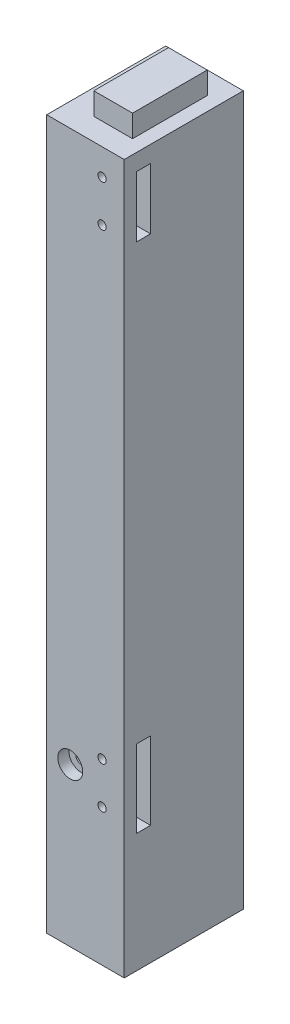
SolidWorks part; units mm, degrees
ref_plane "Front Plane" through (0, 0, 0) normal (0, 0, 1) x (1, 0, 0)
ref_plane "Top Plane" through (0, 0, 0) normal (0, 1, 0) x (1, 0, 0)
ref_plane "Right Plane" through (0, 0, 0) normal (1, 0, 0) x (0, 0, -1)
sketch "Sketch1" plane through (0, 0, 0) normal (0, 0, 1) x (1, 0, 0)
  line L1 (44.45, 406.4) -> (-44.45, 406.4)
  line L2 (44.45, 406.4) -> (44.45, -406.4)
  line L3 (44.45, -406.4) -> (-44.45, -406.4)
  line L4 (-44.45, 406.4) -> (-44.45, -406.4)
  line L5 (44.45, 406.4) -> (-44.45, -406.4) construction
  line L6 (44.45, -406.4) -> (-44.45, 406.4) construction
  point P0 (0, 0)
  dimension "D1" = 812.8
  dimension "D2" = 88.9
extrude "Boss-Extrude1" add sketch "Sketch1" along normal blind 136.525
sketch "Sketch2" plane through (0, 406.4, 0) normal (0, 1, 0) x (1, 0, 0)
  line L0 (-44.45, -136.525) -> (-44.45, 0) construction
  line L1 (-15.875, -25.4) -> (28.575, -25.4)
  line L2 (-15.875, -25.4) -> (-15.875, -111.125)
  line L3 (-15.875, -111.125) -> (28.575, -111.125)
  line L4 (28.575, -25.4) -> (28.575, -111.125)
  line L5 (-15.875, -25.4) -> (28.575, -111.125) construction
  line L6 (-15.875, -111.125) -> (28.575, -25.4) construction
  line L7 (44.45, 0) -> (-44.45, 0) construction
  point P0 (6.35, -68.2625)
  dimension "D1" = 85.725
  dimension "D2" = 28.575
  dimension "D3" = 44.45
  dimension "D4" = 25.4
extrude "Boss-Extrude2" add sketch "Sketch2" along normal blind 25.4 contours L2 L3 L4 L1
sketch "Sketch4" plane through (44.45, 0, 0) normal (1, 0, 0) x (0, 0, -1)
  line L0 (-136.525, 406.4) -> (0, 406.4) construction
  line L1 (-122.2375, -180.975) -> (-106.3625, -180.975)
  line L2 (-122.2375, -180.975) -> (-122.2375, -269.875)
  line L3 (-122.2375, -269.875) -> (-106.3625, -269.875)
  line L4 (-106.3625, -180.975) -> (-106.3625, -269.875)
  line L5 (-122.2375, -180.975) -> (-106.3625, -269.875) construction
  line L6 (-122.2375, -269.875) -> (-106.3625, -180.975) construction
  line L7 (-122.2375, 387.35) -> (-106.3625, 387.35)
  line L8 (-122.2375, 387.35) -> (-122.2375, 317.5)
  line L9 (-122.2375, 317.5) -> (-106.3625, 317.5)
  line L10 (-106.3625, 387.35) -> (-106.3625, 317.5)
  line L11 (-122.2375, 387.35) -> (-106.3625, 317.5) construction
  line L12 (-122.2375, 317.5) -> (-106.3625, 387.35) construction
  line L14 (-136.525, -406.4) -> (-136.525, 406.4) construction
  line L15 (-136.525, -406.4) -> (0, -406.4) construction
  point P0 (-114.3, -225.425)
  point P5 (-114.3, 352.425)
  point P12 (-102.9221, 352.425)
  point P17 (-68.2625, -406.4)
  dimension "D1" = 69.85
  dimension "D2" = 19.05
  dimension "D3" = 15.875
  dimension "D4" = 14.2875
  dimension "D5" = 88.9
  dimension "D6" = 136.525
  dimension "D7" = 15.875
extrude "Cut-Extrude1" cut sketch "Sketch4" against normal blind 50.8
sketch "Sketch5" plane through (0, 0, 0) normal (0, 0, -1) x (-1, 0, 0)
  line L0 (44.45, -406.4) -> (-44.45, -406.4) construction
  line L1 (30.1625, -184.15) -> (4.7625, -184.15)
  line L2 (30.1625, -184.15) -> (30.1625, -266.7)
  line L3 (30.1625, -266.7) -> (4.7625, -266.7)
  line L4 (4.7625, -184.15) -> (4.7625, -266.7)
  line L5 (30.1625, -184.15) -> (4.7625, -266.7) construction
  line L6 (30.1625, -266.7) -> (4.7625, -184.15) construction
  line L7 (44.45, 406.4) -> (44.45, -406.4) construction
  point P0 (17.4625, -225.425)
  dimension "D1" = 25.4
  dimension "D2" = 82.55
  dimension "D3" = 139.7
  dimension "D4" = 14.2875
extrude "Cut-Extrude2" cut sketch "Sketch5" against normal blind 50.8
sketch "Sketch6" plane through (0, 0, 136.525) normal (0, 0, 1) x (1, 0, 0)
  line L0 (-4.7625, -184.15) -> (-4.7625, -266.7) construction
  line L1 (-4.7625, -266.7) -> (-30.1625, -266.7) construction
  line L2 (-30.1625, -266.7) -> (-30.1625, -184.15) construction
  line L3 (-30.1625, -184.15) -> (-4.7625, -184.15) construction
  line L4 (44.45, -180.975) -> (44.45, -269.875) construction
  line L5 (44.45, -269.875) -> (-6.35, -269.875) construction
  line L6 (-6.35, -269.875) -> (-6.35, -180.975) construction
  line L7 (-6.35, -180.975) -> (44.45, -180.975) construction
  line L8 (44.45, 387.35) -> (44.45, 317.5) construction
  line L9 (44.45, 317.5) -> (-6.35, 317.5) construction
  line L10 (-6.35, 317.5) -> (-6.35, 387.35) construction
  line L11 (-6.35, 387.35) -> (44.45, 387.35) construction
  line L12 (-4.7625, -184.15) -> (-4.7625, -266.7)
  line L13 (-4.7625, -266.7) -> (-30.1625, -266.7)
  line L14 (-30.1625, -266.7) -> (-30.1625, -184.15)
  line L15 (-30.1625, -184.15) -> (-4.7625, -184.15)
  line L16 (44.45, -180.975) -> (44.45, -269.875)
  line L17 (44.45, -269.875) -> (-6.35, -269.875)
  line L18 (-6.35, -269.875) -> (-6.35, -180.975)
  line L19 (-6.35, -180.975) -> (44.45, -180.975)
  line L20 (44.45, 387.35) -> (44.45, 317.5)
  line L21 (44.45, 317.5) -> (-6.35, 317.5)
  line L22 (-6.35, 317.5) -> (-6.35, 387.35)
  line L23 (-6.35, 387.35) -> (44.45, 387.35)
  line L24 (-30.1625, -184.15) -> (-4.7625, -266.7) construction
  line L25 (19.05, 387.35) -> (19.05, 317.5) construction
  line L26 (19.05, -180.975) -> (19.05, -269.875) construction
  circle A0 centre (-17.4625, -225.425) radius 6.35
  circle A1 centre (-17.4625, -225.425) radius 14.2875
  circle A2 centre (19.05, 376.2375) radius 4.7625
  circle A3 centre (19.05, 328.6125) radius 4.7625
  circle A4 centre (19.05, -249.2375) radius 4.7625
  circle A5 centre (19.05, -201.6125) radius 4.7625
  point P21 (19.05, 352.425)
  point P28 (19.05, -225.425)
  dimension "D1" = 12.7
  dimension "D2" = 28.575
  dimension "D3" = 9.525
  dimension "D4" = 23.8125
  dimension "D7" = 9.525
  dimension "D8" = 23.8125
  dimension "D9" = 23.8125
  dimension "D5" = 23.8125
  dimension "D6" = 25.4
  dimension "D10" = 25.4
extrude "Cut-Extrude3" cut sketch "Sketch6" against normal blind 12.7 contours A1
sketch "Sketch7" plane through (0, 0, 123.825) normal (0, 0, 1) x (1, 0, 0)
  circle A0 centre (-17.4625, -225.425) radius 6.35
  dimension "D1" = 12.7
extrude "Cut-Extrude4" cut sketch "Sketch7" against normal through all
extrude "Cut-Extrude5" cut sketch "Sketch6<4>" against normal blind 44.45 contours A4 | A3 | A5 | A2 region at (19.05, 328.6125, 136.525) region at (19.05, -249.2375, 136.525)
sketch "Sketch6<4>" plane through (0, 0, 136.525) normal (0, 0, 1) x (1, 0, 0) same geometry as "Sketch6"
